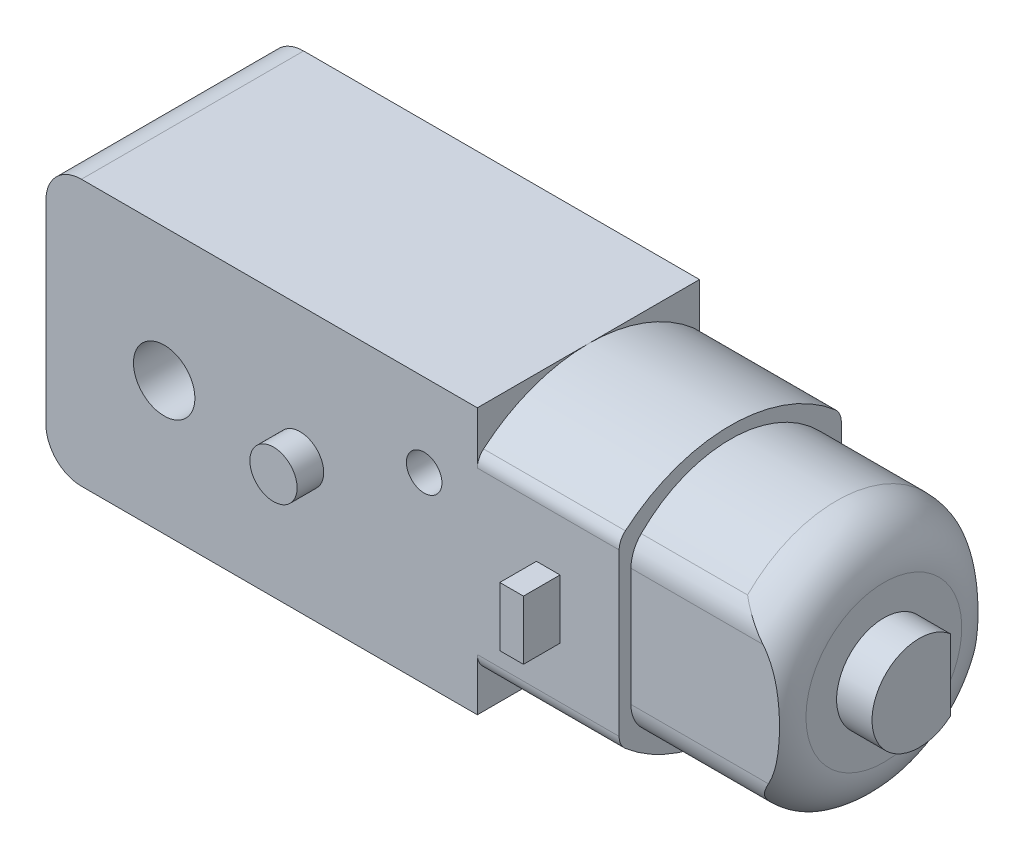
SolidWorks part; units mm, degrees
material "ABS PC"
ref_plane "前视基准面" through (0, 0, 0) normal (0, 0, 1) x (1, 0, 0)
ref_plane "上视基准面" through (0, 0, 0) normal (0, 1, 0) x (1, 0, 0)
ref_plane "右视基准面" through (0, 0, 0) normal (1, 0, 0) x (0, 0, -1)
sketch "草图1" plane through (0, 0, 0) normal (0, 1, 0) x (1, 0, 0)
  line L1 (-18.25, 9.4) -> (18.25, 9.4)
  line L2 (-18.25, 9.4) -> (-18.25, -9.4)
  line L3 (-18.25, -9.4) -> (18.25, -9.4)
  line L4 (18.25, 9.4) -> (18.25, -9.4)
  line L5 (-18.25, 9.4) -> (18.25, -9.4) construction
  line L6 (-18.25, -9.4) -> (18.25, 9.4) construction
  point P0 (0, 0)
  dimension "D1" = 36.5
  dimension "D2" = 18.8
extrude "凸台-拉伸1" add sketch "草图1" along normal blind 22.5
fillet "圆角1" radius 3 2 edges at (-18.25, 0, 0) (-18.25, 22.5, 0)
sketch "草图2" plane through (0, 0, 9.4) normal (0, 0, 1) x (1, 0, 0)
  line L0 (18.25, 22.5) -> (18.25, 0) construction
  line L1 (-18.25, 19.5) -> (-18.25, 3) construction
  circle A0 centre (-8.25, 11.25) radius 2.6
  point P2 (0, 0)
  point P5 (18.25, 11.25)
  dimension "D2" = 5.2
  dimension "D1" = 10
extrude "切除-拉伸1" cut sketch "草图2" against normal through all
sketch "草图3" plane through (-18.25, 0, 0) normal (-1, 0, 0) x (0, 0, 1)
  line L0 (-9.4, 19.5) -> (9.4, 3) construction
  line L1 (9.4, 19.5) -> (-9.4, 3) construction
  line L3 (-1.2, 13.75) -> (1.2, 13.75)
  line L4 (-1.2, 13.75) -> (-1.2, 8.75)
  line L5 (-1.2, 8.75) -> (1.2, 8.75)
  line L6 (1.2, 13.75) -> (1.2, 8.75)
  line L7 (-1.2, 13.75) -> (1.2, 8.75) construction
  line L8 (-1.2, 8.75) -> (1.2, 13.75) construction
  point P8 (0, 11.25)
  point P9 (0, 11.25)
  dimension "D1" = 5
  dimension "D2" = 2.4
extrude "凸台-拉伸2" add sketch "草图3" along normal blind 5
sketch "草图4" plane through (0, 0, 1.2) normal (0, 0, 1) x (1, 0, 0)
  circle A0 centre (-20.56, 11.3164) radius 1.4
  dimension "D1" = 2.8
extrude "切除-拉伸2" cut sketch "草图4" against normal through all
sketch "草图5" plane through (18.25, 0, 0) normal (1, 0, 0) x (0, 0, -1)
  line L0 (-9.4, 22.5) -> (9.4, 0) construction
  line L1 (9.4, 22.5) -> (-9.4, 0) construction
  line L2 (9.4, 22.5) -> (9.4, 0) construction
  line L3 (-9.4, 18.75) -> (9.4, 18.75) construction
  line L4 (-9.4, 18.0831) -> (-9.4, 4.4169)
  line L5 (-9.4, 3.75) -> (9.4, 3.75) construction
  line L6 (9.4, 18.0831) -> (9.4, 4.4169)
  line L7 (-9.4, 18.75) -> (9.4, 3.75) construction
  line L8 (-9.4, 3.75) -> (9.4, 18.75) construction
  line L9 (-9.4, 22.5) -> (9.4, 22.5) construction
  arc A0 (-8.8748, 19.2231) -> (8.8748, 19.2231) centre (0, 8.8437) cw
  arc A1 (-8.8748, 3.2769) -> (8.8748, 3.2769) centre (0, 13.6563) ccw
  arc A2 (-9.4, 4.4169) -> (-8.8748, 3.2769) centre (-7.9, 4.4169) ccw
  arc A3 (8.8748, 3.2769) -> (9.4, 4.4169) centre (7.9, 4.4169) ccw
  arc A4 (9.4, 18.0831) -> (8.8748, 19.2231) centre (7.9, 18.0831) ccw
  arc A5 (-9.4, 18.0831) -> (-8.8748, 19.2231) centre (-7.9, 18.0831) cw
  point P8 (0, 11.25)
  dimension "D2" = 1.5
  dimension "D1" = 15
extrude "凸台-拉伸3" add sketch "草图5" along normal blind 12
sketch "草图6" plane through (30.25, 0, 0) normal (1, 0, 0) x (0, 0, -1)
  line L0 (-9.4, 18.0831) -> (9.4, 4.4169) construction
  line L1 (-9.4, 18.0831) -> (-9.4, 4.4169) construction
  line L2 (-8.4, 17.3561) -> (8.4, 17.3561) construction
  line L3 (-8.4, 17.3561) -> (-8.4, 5.1439)
  line L4 (-8.4, 5.1439) -> (8.4, 5.1439) construction
  line L5 (8.4, 17.3561) -> (8.4, 5.1439)
  line L6 (-8.4, 17.3561) -> (8.4, 5.1439) construction
  line L7 (-8.4, 5.1439) -> (8.4, 17.3561) construction
  line L9 (-8.4077, 21.4961) -> (8.4077, 21.4961) construction
  line L10 (-8.4077, 21.4961) -> (-8.4077, 1.0039) construction
  line L11 (-8.4077, 1.0039) -> (8.4077, 1.0039) construction
  line L12 (8.4077, 21.4961) -> (8.4077, 1.0039) construction
  line L13 (-8.4077, 21.4961) -> (8.4077, 1.0039) construction
  line L14 (-8.4077, 1.0039) -> (8.4077, 21.4961) construction
  arc A0 (-8.4, 17.3561) -> (8.4, 17.3561) centre (0, 10.9044) cw
  arc A1 (-8.4, 5.1439) -> (8.4, 5.1439) centre (0, 11.5956) ccw
  point P4 (0, 11.25)
  point P13 (0, 11.25)
  dimension "D1" = 1
  dimension "D2" = 4.14
extrude "凸台-拉伸4" add sketch "草图6" along normal blind 13
fillet "圆角2" radius 3 4 edges at (36.75, 17.3561, -8.4) (36.75, 5.1439, -8.4) (36.75, 5.1439, 8.4) (36.75, 17.3561, 8.4)
fillet "圆角3" radius 4 1 edges at (43.25, 21.4961, 0) tangent propagation no
sketch "草图7" plane through (43.25, 0, 0) normal (1, 0, 0) x (0, 0, -1)
  line L0 (2.6458, 7.9044) -> (2.6458, 13.9044)
  arc A0 (2.6458, 13.9044) -> (2.6458, 7.9044) centre (0, 10.9044) ccw
  dimension "D1" = 8
  dimension "D2" = 6
extrude "凸台-拉伸5" add sketch "草图7" along normal blind 3
sketch "草图8" plane through (46.25, 0, 0) normal (1, 0, 0) x (0, 0, -1)
  circle A0 centre (0, 10.9044) radius 1
  dimension "D1" = 2
sketch "草图9" plane through (0, 0, -9.4) normal (0, 0, -1) x (-1, 0, 0)
  line L0 (-30.25, 4.4169) -> (-30.25, 18.0831) construction
  line L1 (-18.25, 4.4169) -> (-18.25, 0) construction
  circle A0 centre (-3.25, 11.25) radius 2
  point P2 (0, 0)
  point P5 (0, 0)
  point P6 (-30.25, 11.25)
  dimension "D2" = 4
  dimension "D1" = 15
extrude "凸台-拉伸7" add sketch "草图9" against normal blind 21.05
sketch "草图10" plane through (0, 0, 0) normal (0, 0, 1) x (1, 0, 0)
  line L0 (18.25, 18.0831) -> (30.25, 4.4169) construction
  line L2 (23.25, 13.75) -> (25.25, 13.75)
  line L3 (23.25, 13.75) -> (23.25, 8.75)
  line L4 (23.25, 8.75) -> (25.25, 8.75)
  line L5 (25.25, 13.75) -> (25.25, 8.75)
  line L6 (23.25, 13.75) -> (25.25, 8.75) construction
  line L7 (23.25, 8.75) -> (25.25, 13.75) construction
  point P4 (24.25, 11.25)
  point P5 (24.25, 11.25)
  dimension "D1" = 5
  dimension "D2" = 2
extrude "凸台-拉伸8" add sketch "草图10" along normal mid plane 25
sketch "草图11" plane through (0, 0, 9.4) normal (0, 0, 1) x (1, 0, 0)
  line L0 (-18.25, 19.5) -> (-18.25, 3) construction
  circle A0 centre (13.75, 15.5) radius 1.5
  point P6 (0, 0)
  point P7 (13.75, 15.5)
  dimension "D2" = 3
  dimension "D1" = 32
extrude "切除-拉伸3" cut sketch "草图11" against normal through all
